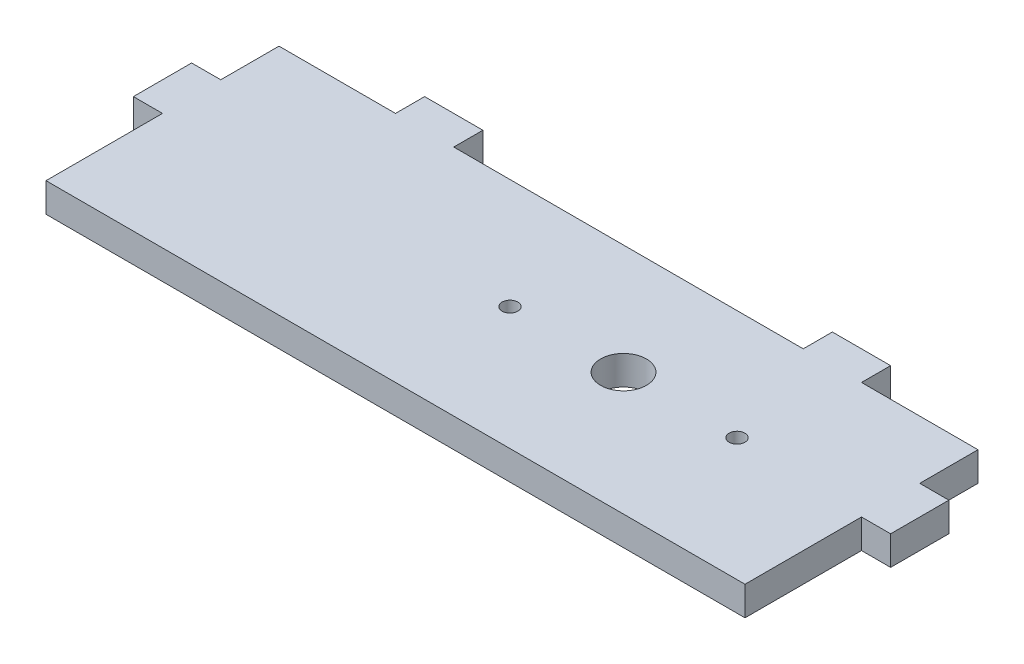
SolidWorks part; units mm, degrees
material "Beech"
ref_plane "Front Plane" through (0, 0, 0) normal (0, 0, 1) x (1, 0, 0)
ref_plane "Top Plane" through (0, 0, 0) normal (0, 1, 0) x (1, 0, 0)
ref_plane "Right Plane" through (0, 0, 0) normal (1, 0, 0) x (0, 0, -1)
sketch "Sketch1" plane through (0, 0, 0) normal (0, 1, 0) x (1, 0, 0)
  line L0 (0, 0) -> (0, 50.8)
  line L1 (0, 0) -> (152.4, 0)
  line L2 (0, 50.8) -> (152.4, 50.8)
  line L3 (152.4, 0) -> (152.4, 50.8)
  line L4 (0, 38.1) -> (-6.35, 38.1)
  line L5 (0, 38.1) -> (0, 25.4)
  line L6 (-6.35, 38.1) -> (-6.35, 25.4)
  line L7 (0, 25.4) -> (-6.35, 25.4)
  line L8 (25.4, 50.8) -> (25.4, 57.15)
  line L9 (25.4, 50.8) -> (38.1, 50.8)
  line L10 (25.4, 57.15) -> (38.1, 57.15)
  line L11 (38.1, 50.8) -> (38.1, 57.15)
  line L12 (114.3, 50.8) -> (114.3, 57.15)
  line L13 (114.3, 50.8) -> (127, 50.8)
  line L14 (114.3, 57.15) -> (127, 57.15)
  line L15 (127, 50.8) -> (127, 57.15)
  line L16 (152.4, 38.1) -> (158.75, 38.1)
  line L17 (152.4, 38.1) -> (152.4, 25.4)
  line L18 (158.75, 38.1) -> (158.75, 25.4)
  line L19 (152.4, 25.4) -> (158.75, 25.4)
  circle A0 centre (99.11, 26.8) radius 5
  circle A1 centre (123.86, 26.8) radius 1.725
  circle A2 centre (74.36, 26.8) radius 1.725
  point P27 (76.2, 50.8)
  dimension "D8" = 10
  dimension "D9" = 3.45
  dimension "D1" = 152.4
  dimension "D2" = 50.8
  dimension "D3" = 12.7
  dimension "D4" = 6.35
  dimension "D5" = 25.4
  dimension "D6" = 25.4
  dimension "D7" = 12.7
  dimension "D10" = 24.75
  dimension "D11" = 24.75
  dimension "D12" = 24
  dimension "D13" = 22.91
extrude "Boss-Extrude1" add sketch "Sketch1" along normal blind 6.35 contours L1 L3 L2 L0 A2 A1 A0 | L2 L11 L10 L8 | L7 L0 L4 L6 | L3 L19 L18 L16 | L2 L15 L14 L12 region at (75.9086, 0, -25.3822) region at (-3.175, 0, -31.75) region at (155.575, 0, -31.75) region at (31.75, 0, -53.975) region at (120.65, 0, -53.975)
equation "\"CageLeftBottomEdge\"=22.11mm"
equation "\"CageLeftTopEdge\"=22.11mm"
equation "\"CageRightBottomEdge\"=21.63mm"
equation "\"CageRightTopEdge\"=21.63mm"
equation "\"CageHeight\"=86.04mm"
equation "\"CageLength\"=73.76mm"
equation "\"CageTopScrewClearance\"=10mm"
equation "\"CageBottomScrewClearance\"=25mm"
equation "\"CageLeftTopDepth\"= 11.65mm"
equation "\"CageLeftBottomDepth\"=11.11mm"
equation "\"CageLeftTopHeight\"=8.56175mm"
equation "\"CageLeftBottomHeight\"=16mm"
equation "\"CageRightTopDepth\"= 11.05mm"
equation "\"CageRightBottomDepth\"=10.58mm"
equation "\"CageRightTopHeight\"=9.6mm"
equation "\"CageRightBottomHeight\"=15.49mm"
equation "\"CageLeftTopChannelDepth\"=2.41908mm"
equation "\"CageLeftBottomChannelDepth\"=2.588mm"
equation "\"CageLeftChannelHeight\"=11.7mm"
equation "\"CageRightTopChannelDepth\"=2.32mm"
equation "\"CageRightBottomChannelDepth\"=2.318mm"
equation "\"CageRightChannelHeight\"=10mm"
equation "\"CageChanRelHeight\"=23.99mm"
equation "\"CageChanRelDepth\"=5.492mm"
equation "\"CageChamberRadius\"=16.261mm"
equation "\"CageScrewDiameter\"=4.8mm"
equation "\"CageSetScrewDiameter\"=3.5mm"
equation "\"CageAxleRadius\"=6.639mm"
equation "\"CageAxleKeyHeight\"=1.619mm"
equation "\"CageAxleKeyWidth\"=2.662mm"
equation "\"CageHoseWindowWidth\"=16.29mm"
equation "\"CageHoseWindowHeight\"=26.5mm"
equation "\"CageHoseWindow-Edge\"=8.89mm"
equation "\"CageScrew-VerticalEdge\"=5.0mm"
equation "\"CageScrew-HorizontalEdge\"=7.5mm"
equation "\"CageScrew-HoseCornerScrewEdge\"=4.45mm"
equation "\"CageAxle-BottomEdge\"=56.05mm"
equation "\"CageAxle-FrontEdge\"=46.03mm"
equation "\"CageBackSetScrew-Axle\"=40mm"
equation "\"CageFrontSetScrew-Axle\"=22mm"
equation "\"CageVelocityWindow-BackEdge\"=34.8mm"
equation "\"CageVelocityWindow-BottomEdge\"=27.55mm"
equation "\"CageVelocityWindowHeight\"=22.29mm"
equation "\"CageVelocityWindowWidth\"=12.61mm"
equation "\"TriggerSlot-BottomEdge\"=6.35mm"
equation "\"TriggerSlot-FrontEdge\"=15mm"
equation "\"TriggerSlotSize\"=6.7mm"
equation "\"TriggerRackOffset\"=.236224in"
equation "\"TriggerSlotSizeInt\"=.25in"
equation "\"MotorMountLegLength\"=.25in"
equation "\"GearOffset\"=.264907in"
equation "\"TriggerSlotSpacing\"=.25in"
equation "\"TriggerMiniSlotWidth\"=3.5mm"
equation "\"TriggerRackWidth\"=6.5mm"
equation "\"TGMGearFaceDiameter\"=24.40mm"
equation "\"TGMCylinderLength\"=15.00mm"
equation "\"TGMScrewHole-Center\"=8.70mm"
equation "\"TGMScrewHoleDiameter\"=5.04mm"
equation "\"TGMCenterHoleDiameter\"=9.50mm"
equation "\"TGMShaftCollarSideLength\"=19.00mm"
equation "\"TGMShaftCollarDockingDepth\"=7.00mm"
equation "\"whitemotordepth\"=11.27mm"
equation "\"whitemotorbackdepth\"=3.845mm"
equation "\"whitemotoraxledepth\" = 3.5mm"
equation "\"whitemotoraxleoffset\"=11.4mm"
equation "\"whitemotorwidth\"=12.07mm"
equation "\"whitemotorheight\"=16.68mm"
equation "\"whitemotorcylinderlength\" =13.04mm"
equation "\"whitemotorcylinderradius\"=3.845mm"
equation "\"whitemotorcylinderoffset\"=2.35mm"
equation "\"whitemotorcutoutlength\"=1.88mm"
equation "\"whitemotorouterrad\"=5mm"
equation "\"whitemotorinnerrad\"=2.95mm"
equation "\"elasticracklength\"=2in"
equation "\"elasticrackpegsize\"=.25in"
equation "\"elasticrackpegbuffer\"=.125in"
equation "\"elasticrackpegspacing\"=1.76476378in"
equation "\"elasticbaybuffer\"=.25in"
equation "\"elasticdepth\"=.125in"
equation "\"elasticbaydepth\"=.75in"
equation "\"motormountwidth\"=12mm"
equation "\"motormountcornerfillet\"=3mm"
equation "\"pandiscradius\"=14in"
equation "\"towermaterialwidth\"=.25in"
equation "\"towerslotlength\"=.5in"
equation "\"towermarkerspace\"=5in"
equation "\"towerslothorizoffset\"=1in"
equation "\"towerslothorizspacing\"=2in"
equation "\"towerslotvertoffset\"=3in"
equation "\"towerslotvertspacing\"=2in"
equation "\"towerheight\"=12in"
equation "\"towerupslot\"=1in"
equation "\"toweraxle\"=.5in"
equation "\"towerplatslotoffset\"=1.5in"
equation "\"towermotorpanelheight\"=10in"
equation "\"D1@Sketch1\"=(\"towerslothorizspacing\"+\"towerslothorizoffset\")*2"
equation "\"towerplatdepth\"=2in"
equation "\"D2@Sketch1\"=\"towerplatdepth\""
equation "\"D3@Sketch1\"=\"towerslotlength\""
equation "\"D4@Sketch1\"=\"towermaterialwidth\""
equation "\"D5@Sketch1\"=\"towerplatslotoffset\"-\"towerslotlength\""
equation "\"D6@Sketch1\"=\"towerplatslotoffset\"-\"towerslotlength\""
equation "\"D7@Sketch1\"=\"towerslotlength\""
equation "\"stepperouterrad\"=10mm"
equation "\"D8@Sketch1\"=\"stepperouterrad\""
equation "\"stepperscrewsize\"=3.45mm"
equation "\"D9@Sketch1\"=\"stepperscrewsize\""
equation "\"stepperscrewc2c\"=49.5mm"
equation "\"D10@Sketch1\"=\"stepperscrewc2c\"/2"
equation "\"D11@Sketch1\"=\"stepperscrewc2c\"/2"
equation "\"stepperdepthoffset\"=24mm"
equation "\"D12@Sketch1\"=\"stepperdepthoffset\""
equation "\"stepperhorizoffset\"=22.91mm"
equation "\"D13@Sketch1\"=\"stepperhorizoffset\""
equation "\"D1@Boss-Extrude1\"=\"towermaterialwidth\""
equation "\"shaftslotOD\"=18.8mm"
equation "\"shaftslotID\"=13.28mm"
equation "\"shaftkeywidth\"=2.67mm"
equation "\"shaftkeydepth\"=1.8mm"
equation "\"shaftcollartotaldepth\"=12.5mm"
equation "\"shaftsquaredepth\"=6mm"
equation "\"shaftsetscrewsize\"=3.5mm"
equation "\"shaftkeytightdepth\"=1.85mm"
equation "\"shaftslottightID\"=12.78mm"
equation "\"shaftsetscrewoffset\"=9mm"
equation "\"cagecollartotaldepth\"=10mm"
equation "\"cagecollartotalwidth\"=35mm"
equation "\"cagecollarbasedepth\"=4mm"
